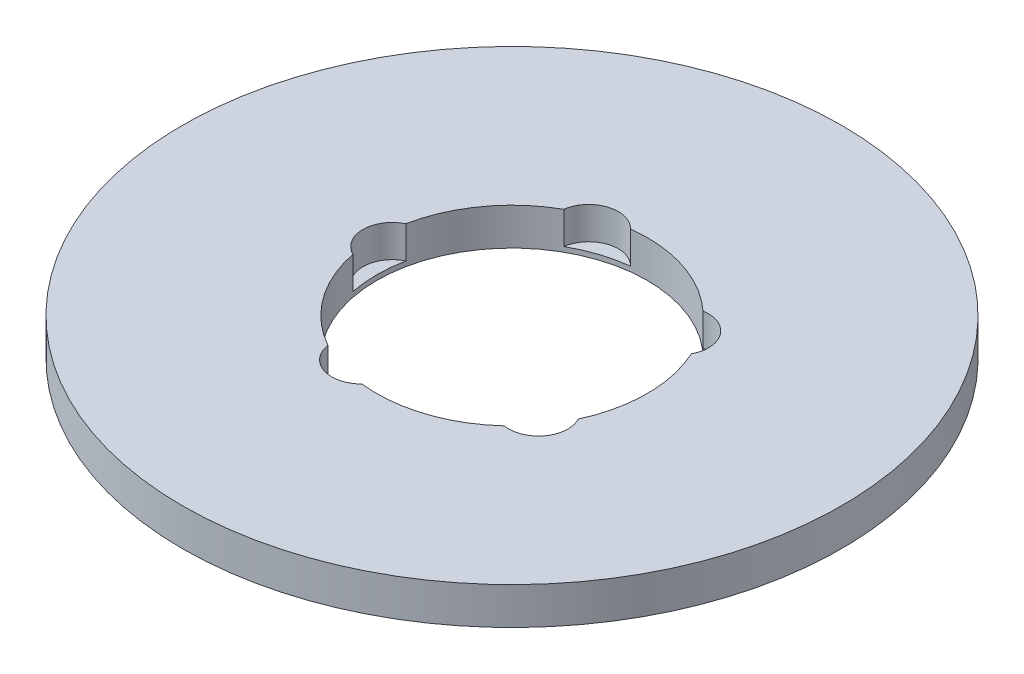
SolidWorks part; units mm, degrees
ref_plane "Front Plane" through (0, 0, 0) normal (0, 0, 1) x (1, 0, 0)
ref_plane "Top Plane" through (0, 0, 0) normal (0, 1, 0) x (1, 0, 0)
ref_plane "Right Plane" through (0, 0, 0) normal (1, 0, 0) x (0, 0, -1)
sketch "Sketch1" plane through (0, 0, 0) normal (0, 1, 0) x (1, 0, 0)
  circle A0 centre (0, 0) radius 97.5
  dimension "FLANGE_OD" = 195
extrude "Boss-Extrude1" add sketch "Sketch1" along normal blind 11
sketch "Sketch2" plane through (0, 0, 0) normal (0, 1, 0) x (1, 0, 0)
  circle A0 centre (0, 0) radius 40
  dimension "BORE_D" = 80
extrude "Cut-Extrude1" cut sketch "Sketch2" along normal through all
sketch "Sketch3" plane through (0, 11, 0) normal (0, 1, 0) x (1, 0, 0)
  circle A0 centre (0, 0) radius 35.3866 construction
  circle A1 centre (-35.3866, 0) radius 8.7243
  dimension "BOLT_D" = 17.4485
  dimension "BOLT_PCD" = 70.7733
extrude "Cut-Extrude2" cut sketch "Sketch3" against normal blind 9.547
pattern_circular "CirPattern1" count 5 over 360 about axis through (0, 0, 0) along (0, 1, 0) of "Cut-Extrude2"
